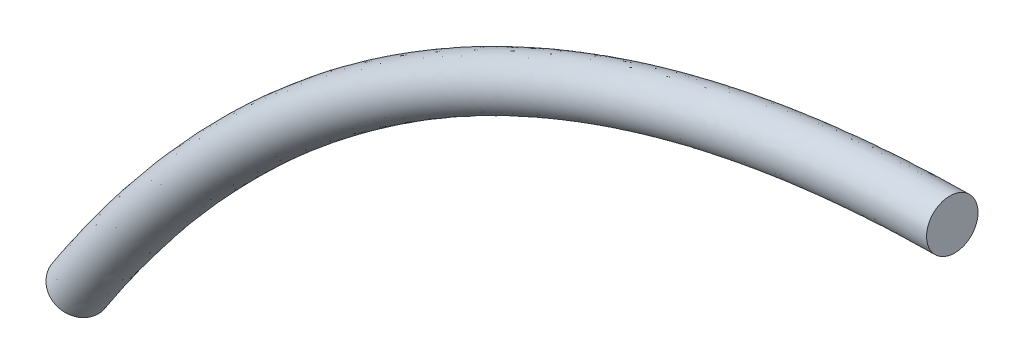
SolidWorks part; units mm, degrees
material "Custom Plastic"
ref_plane "X-Y Datum" through (0, 0, 0) normal (0, 0, 1) x (1, 0, 0)
ref_plane "X-Z Datum" through (0, 0, 0) normal (0, 1, 0) x (1, 0, 0)
ref_plane "Y-Z Datum" through (0, 0, 0) normal (1, 0, 0) x (0, 0, -1)
sketch3d "3DSketch1"
  circle A0 centre (-244.2256, -166.5107, 163.3218) radius 2.9 construction
  circle A1 centre (-71.1484, -53.4906, 183.2483) radius 2.5781 construction
  circle A3 centre (-244.2256, -166.5107, 163.3218) radius 3.475 construction
  spline S0 degree 2 poles (-244.2256, -166.5107, 163.3218) (-168.3222, -58.5751, 178.7817) (-56.5066, -52.2024, 183.9814) knots 0 0 0 1 1 1
  point P0 (-244.2256, -166.5107, 163.3218)
  point P1 (-71.1484, -53.4906, 183.2483)
  point P4 (-246.0339, -168.7779, 163.3218)
  point P8 (-73.7124, -53.7601, 183.2483)
  point P16 (-246.3925, -169.2274, 163.3218)
sweep "Sweep1" add path "3DSketch1" circular profile diameter 9.398 parameters "D3"=9.398
